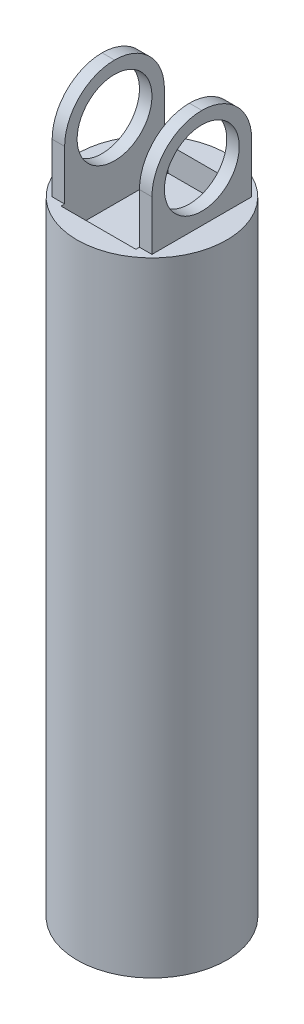
SolidWorks part; units mm, degrees
ref_plane "Front Plane" through (0, 0, 0) normal (0, 0, 1) x (1, 0, 0)
ref_plane "Top Plane" through (0, 0, 0) normal (0, 1, 0) x (1, 0, 0)
ref_plane "Right Plane" through (0, 0, 0) normal (1, 0, 0) x (0, 0, -1)
sketch "Sketch1" plane through (0, 0, 0) normal (0, 1, 0) x (1, 0, 0)
  circle A0 centre (0, 0) radius 3
extrude "Boss-Extrude1" add sketch "Sketch1" along normal blind 25
sketch "Sketch2" plane through (0, 25, 0) normal (0, 1, 0) x (1, 0, 0)
  line L0 (-1.5, 1.5) -> (-1.5, -1.5)
  line L1 (2, 2) -> (-2, 2)
  line L2 (2, 2) -> (2, -2)
  line L3 (2, -2) -> (-2, -2)
  line L4 (-2, 2) -> (-2, -2)
  line L5 (2, 2) -> (-2, -2) construction
  line L6 (2, -2) -> (-2, 2) construction
  line L7 (1.5, -1.5) -> (-1.5, -1.5)
  line L8 (1.5, 1.5) -> (1.5, -1.5)
  line L9 (1.5, 1.5) -> (-1.5, 1.5)
  point P0 (0, 0)
  dimension "D1" = 4
  dimension "D2" = 4
  dimension "D3" = 0.5
extrude "Boss-Extrude2" add sketch "Sketch2" along normal blind 4
sketch "Sketch3" plane through (0, 29, 0) normal (0, 1, 0) x (1, 0, 0)
  line L1 (1.5, 2.1441) -> (-1.5, 2.1441)
  line L2 (1.5, 2.1441) -> (1.5, -2.1441)
  line L3 (1.5, -2.1441) -> (-1.5, -2.1441)
  line L4 (-1.5, 2.1441) -> (-1.5, -2.1441)
  line L5 (1.5, 2.1441) -> (-1.5, -2.1441) construction
  line L6 (1.5, -2.1441) -> (-1.5, 2.1441) construction
  point P0 (0, 0)
extrude "Cut-Extrude1" cut sketch "Sketch3" against normal blind 5
sketch "Sketch4" plane through (-2, 0, 0) normal (-1, 0, 0) x (0, 0, 1)
  line L0 (0, 29) -> (0, 27)
  line L1 (-2, 29) -> (2, 29) construction
  circle A0 centre (0, 27) radius 1.5
extrude "Cut-Extrude2" cut sketch "Sketch4" against normal blind 5 contours A0 region at (-2, 25.9693, -1.0307)
fillet "Fillet1" radius 2 4 edges at (1.75, 29, 2) (1.75, 29, -2) (-1.75, 29, -2) (-1.75, 29, 2)
